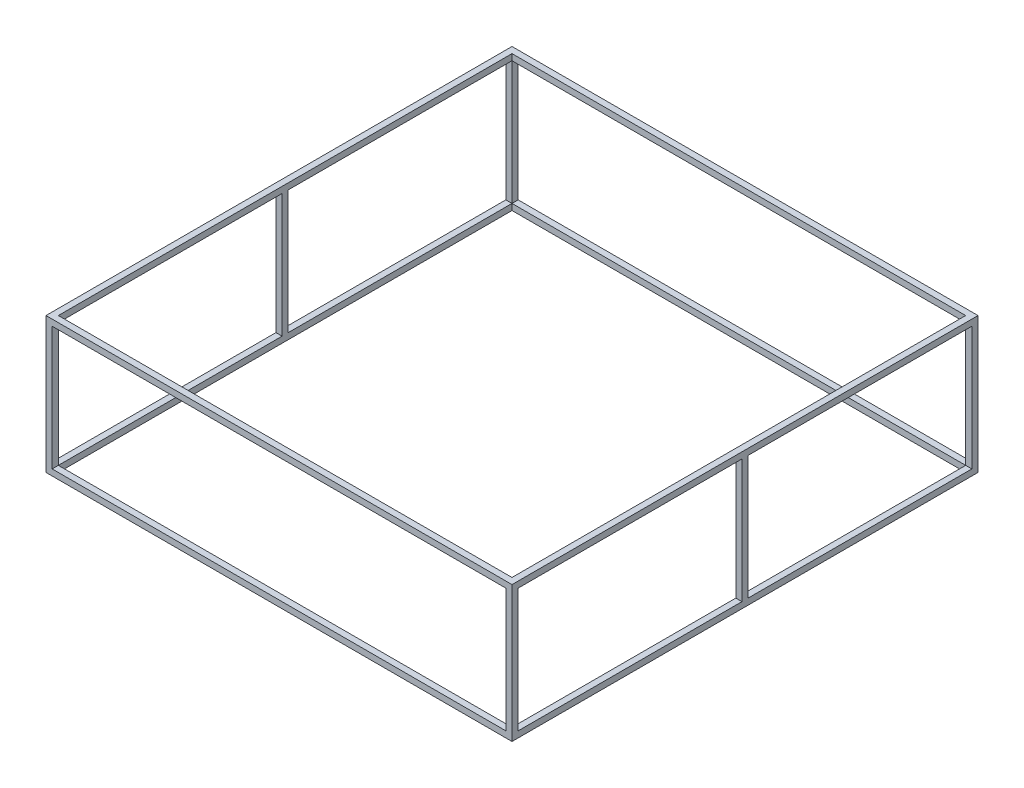
SolidWorks part; units mm, degrees
ref_plane "Front Plane" through (0, 0, 0) normal (0, 0, 1) x (1, 0, 0)
ref_plane "Top Plane" through (0, 0, 0) normal (0, 1, 0) x (1, 0, 0)
ref_plane "Right Plane" through (0, 0, 0) normal (1, 0, 0) x (0, 0, -1)
sketch "Sketch1" plane through (0, 0, 0) normal (0, 1, 0) x (1, 0, 0)
  line L0 (-584.125, 584.125) -> (-584.125, -584.125)
  line L1 (-600, 600) -> (600, 600)
  line L2 (-600, 600) -> (-600, -600)
  line L3 (-600, -600) -> (600, -600)
  line L4 (600, 600) -> (600, -600)
  line L5 (-600, 600) -> (600, -600) construction
  line L6 (-600, -600) -> (600, 600) construction
  line L7 (-584.125, -584.125) -> (584.125, -584.125)
  line L8 (584.125, 584.125) -> (584.125, -584.125)
  line L9 (-584.125, 584.125) -> (584.125, 584.125)
  point P0 (0, 0)
  dimension "D1" = 1200
  dimension "D2" = 1200
  dimension "D3" = 15.875
extrude "Boss-Extrude1" add sketch "Sketch1" along normal blind 15.875
sketch "Sketch2" plane through (0, 15.875, 0) normal (0, 1, 0) x (1, 0, 0)
  line L0 (-584.125, 584.125) -> (-584.125, -584.125) construction
  line L1 (-600, 600) -> (-584.125, 600)
  line L2 (-600, 600) -> (-600, 584.125)
  line L3 (-600, 584.125) -> (-584.125, 584.125)
  line L4 (-584.125, 600) -> (-584.125, 584.125)
  line L5 (584.125, 584.125) -> (-584.125, 584.125) construction
  line L6 (-600, 600) -> (-600, -600) construction
  line L7 (-600, -600) -> (-584.125, -600)
  line L8 (-600, -600) -> (-600, -584.125)
  line L9 (-600, -584.125) -> (-584.125, -584.125)
  line L10 (-584.125, -600) -> (-584.125, -584.125)
  line L11 (-600, 7.9375) -> (-584.125, 7.9375)
  line L12 (-600, 7.9375) -> (-600, -7.9375)
  line L13 (-600, -7.9375) -> (-584.125, -7.9375)
  line L14 (-584.125, 7.9375) -> (-584.125, -7.9375)
  point P21 (-600, 0)
  dimension "D1" = 15.875
extrude "Boss-Extrude2" add sketch "Sketch2" along normal blind 318.25
sketch "Sketch3" plane through (0, 334.125, 0) normal (0, 1, 0) x (1, 0, 0)
  line L4 (600, 600) -> (-600, 600)
  line L5 (600, -600) -> (600, 600)
  line L6 (-600, -600) -> (600, -600)
  line L7 (-600, 600) -> (-600, -600)
  line L8 (600, 600) -> (-600, 600)
  line L9 (600, -600) -> (600, 600)
  line L10 (-600, -600) -> (600, -600)
  line L11 (-600, 600) -> (-600, -600)
  line L12 (-584.125, 584.125) -> (-584.125, -584.125)
  line L13 (-584.125, -584.125) -> (584.125, -584.125)
  line L14 (584.125, -584.125) -> (584.125, 584.125)
  line L15 (584.125, 584.125) -> (-584.125, 584.125)
  line L16 (-584.125, 584.125) -> (-584.125, -584.125)
  line L17 (-584.125, -584.125) -> (584.125, -584.125)
  line L18 (584.125, -584.125) -> (584.125, 584.125)
  line L19 (584.125, 584.125) -> (-584.125, 584.125)
  dimension "D1" = 0
  dimension "D2" = 0
extrude "Boss-Extrude3" add sketch "Sketch3" along normal blind 15.875
mirror "Mirror1" about plane through (0, 0, 0) normal (1, 0, 0) of "Boss-Extrude2"
